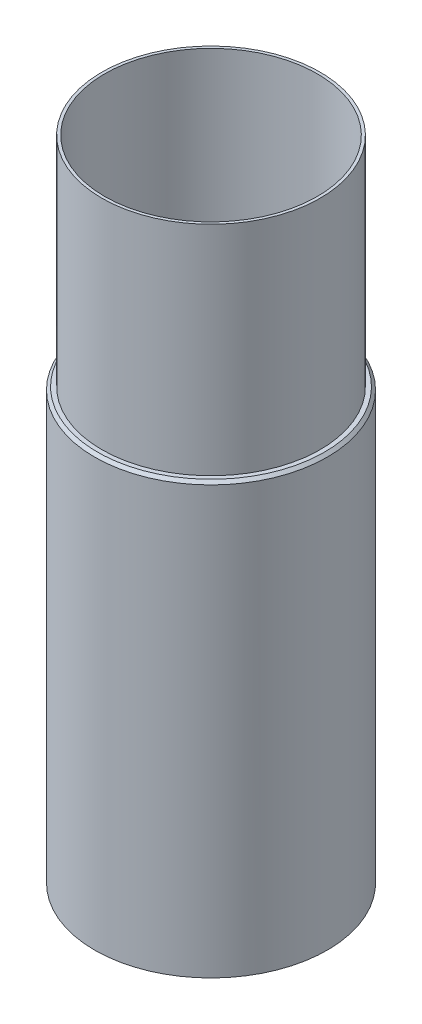
SolidWorks part; units mm, degrees
material "A-Glass Fiber"
ref_plane "Front Plane" through (0, 0, 0) normal (0, 0, 1) x (1, 0, 0)
ref_plane "Top Plane" through (0, 0, 0) normal (0, 1, 0) x (1, 0, 0)
ref_plane "Right Plane" through (0, 0, 0) normal (1, 0, 0) x (0, 0, -1)
sketch "Sketch1" plane through (0, 0, 0) normal (0, 0, 1) x (1, 0, 0)
  line L0 (81.2, 0) -> (81.2, 300)
  line L1 (76.2, 0) -> (76.2, 300)
  line L2 (81.2, 300) -> (76.2, 300)
  line L3 (76.2, 0) -> (81.2, 0)
  line L4 (0, 204.6154) -> (0, 85.8935) construction
  dimension "D1" = 76.2
  dimension "D2" = 300
  dimension "D3" = 5
revolve "Revolve1" add sketch "Sketch1" angle 360 about L4
sketch "Sketch3" plane through (0, 300, 0) normal (0, 1, 0) x (1, 0, 0)
  circle A0 centre (0, 0) radius 76.2
  circle A1 centre (0, 0) radius 74.2
  circle A2 centre (0, 0) radius 76.2 construction
  dimension "D1" = 2
extrude "Boss-Extrude1" add sketch "Sketch3" along normal blind 152 and the other way blind 152
chamfer "Chamfer1" distance 2 angle 45 1 edges at (0, 300, 81.2)
